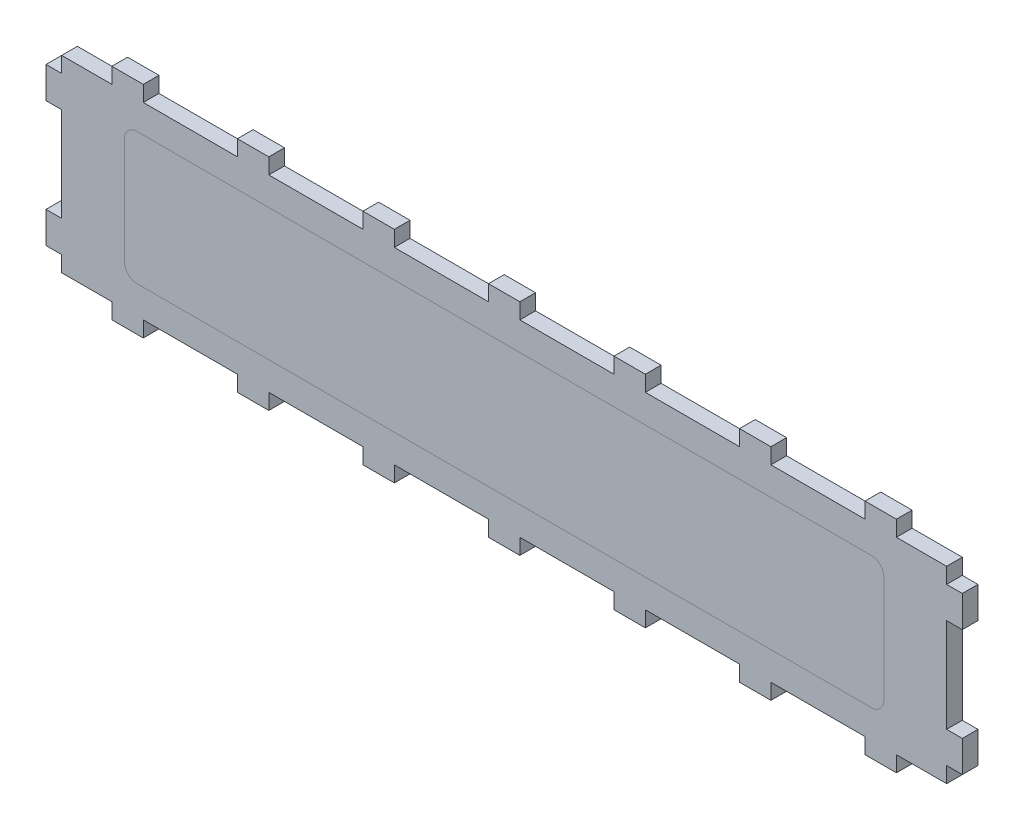
SolidWorks part; units mm, degrees
material "Maple"
ref_plane "Front" through (0, 0, 0) normal (0, 0, 1) x (1, 0, 0)
ref_plane "Top" through (0, 0, 0) normal (0, 1, 0) x (1, 0, 0)
ref_plane "Right" through (0, 0, 0) normal (1, 0, 0) x (0, 0, -1)
sketch "Sketch1" plane through (0, 0, 0) normal (0, 0, 1) x (1, 0, 0)
  line L0 (-73, 15) -> (73, 15) construction
  line L1 (-73, -17.5) -> (73, -17.5) construction
  line L2 (-73, -17.5) -> (-73, 17.5) construction
  line L3 (-73, 17.5) -> (73, 17.5) construction
  line L4 (73, -17.5) -> (73, 17.5) construction
  line L5 (-73, -17.5) -> (73, 17.5) construction
  line L6 (-73, 17.5) -> (73, -17.5) construction
  line L7 (70.5, 17.5) -> (70.5, -17.5) construction
  line L8 (-12.0378, 0) -> (10.199, 0) construction
  line L9 (0, 8.2237) -> (0, -7.5658) construction
  line L10 (-70.5, 17.5) -> (-70.5, -17.5) construction
  line L11 (-73, -15) -> (73, -15) construction
  line L12 (-70.5, -12.5) -> (-70.5, -15)
  line L13 (-70.5, -12.5) -> (-73, -12.5)
  line L14 (-73, -12.5) -> (-73, -7.5)
  line L15 (-73, -7.5) -> (-70.5, -7.5)
  line L16 (-70.5, -7.5) -> (-70.5, 7.5)
  line L17 (-70.5, -15) -> (-62.5, -15)
  line L18 (-62.5, -15) -> (-62.5, -17.5)
  line L19 (-62.5, -17.5) -> (-57.5, -17.5)
  line L20 (-57.5, -17.5) -> (-57.5, -15)
  line L21 (-57.5, -15) -> (-42.5, -15)
  line L22 (-70.5, 12.5) -> (-73, 12.5)
  line L23 (-73, 7.5) -> (-70.5, 7.5)
  line L24 (-73, 12.5) -> (-73, 7.5)
  line L25 (-70.5, 15) -> (-70.5, 12.5)
  line L26 (-42.5, -15) -> (-42.5, -17.5)
  line L27 (-42.5, -17.5) -> (-37.5, -17.5)
  line L28 (-37.5, -17.5) -> (-37.5, -15)
  line L29 (-37.5, -15) -> (-22.5, -15)
  line L30 (-22.5, -15) -> (-22.5, -17.5)
  line L31 (-22.5, -17.5) -> (-17.5, -17.5)
  line L32 (-17.5, -17.5) -> (-17.5, -15)
  line L33 (-17.5, -15) -> (-2.5, -15)
  line L34 (-2.5, -15) -> (-2.5, -17.5)
  line L35 (-2.5, -17.5) -> (2.5, -17.5)
  line L36 (2.5, -17.5) -> (2.5, -15)
  line L37 (17.5, -15) -> (2.5, -15)
  line L38 (17.5, -17.5) -> (17.5, -15)
  line L39 (22.5, -17.5) -> (17.5, -17.5)
  line L40 (22.5, -15) -> (22.5, -17.5)
  line L41 (37.5, -15) -> (22.5, -15)
  line L42 (37.5, -17.5) -> (37.5, -15)
  line L43 (42.5, -17.5) -> (37.5, -17.5)
  line L44 (42.5, -15) -> (42.5, -17.5)
  line L45 (57.5, -15) -> (42.5, -15)
  line L46 (57.5, -17.5) -> (57.5, -15)
  line L47 (62.5, -17.5) -> (57.5, -17.5)
  line L48 (62.5, -15) -> (62.5, -17.5)
  line L49 (70.5, -15) -> (62.5, -15)
  line L50 (62.5, 15) -> (62.5, 17.5)
  line L51 (70.5, -12.5) -> (73, -12.5)
  line L52 (73, -12.5) -> (73, -7.5)
  line L53 (73, -7.5) -> (70.5, -7.5)
  line L54 (70.5, -7.5) -> (70.5, 7.5)
  line L55 (73, 7.5) -> (70.5, 7.5)
  line L56 (73, 12.5) -> (73, 7.5)
  line L57 (70.5, 12.5) -> (73, 12.5)
  line L58 (70.5, 15) -> (70.5, 12.5)
  line L59 (62.5, 17.5) -> (57.5, 17.5)
  line L60 (57.5, 17.5) -> (57.5, 15)
  line L61 (57.5, 15) -> (42.5, 15)
  line L62 (42.5, 15) -> (42.5, 17.5)
  line L63 (42.5, 17.5) -> (37.5, 17.5)
  line L64 (37.5, 17.5) -> (37.5, 15)
  line L65 (37.5, 15) -> (22.5, 15)
  line L66 (22.5, 15) -> (22.5, 17.5)
  line L67 (22.5, 17.5) -> (17.5, 17.5)
  line L68 (17.5, 17.5) -> (17.5, 15)
  line L69 (17.5, 15) -> (2.5, 15)
  line L70 (2.5, 17.5) -> (2.5, 15)
  line L71 (-2.5, 17.5) -> (2.5, 17.5)
  line L72 (-2.5, 15) -> (-2.5, 17.5)
  line L73 (-17.5, 15) -> (-2.5, 15)
  line L74 (-17.5, 17.5) -> (-17.5, 15)
  line L75 (-22.5, 17.5) -> (-17.5, 17.5)
  line L76 (-22.5, 15) -> (-22.5, 17.5)
  line L77 (-37.5, 15) -> (-22.5, 15)
  line L78 (-37.5, 17.5) -> (-37.5, 15)
  line L79 (-42.5, 17.5) -> (-37.5, 17.5)
  line L80 (-42.5, 15) -> (-42.5, 17.5)
  line L81 (-57.5, 15) -> (-42.5, 15)
  line L82 (-57.5, 17.5) -> (-57.5, 15)
  line L83 (-62.5, 17.5) -> (-57.5, 17.5)
  line L84 (-62.5, 15) -> (-62.5, 17.5)
  line L85 (-70.5, 15) -> (-62.5, 15)
  line L86 (70.5, 15) -> (62.5, 15)
  line L87 (70.5, -15) -> (70.5, -12.5)
  line L89 (-58.5, -10.5) -> (58.5, -10.5)
  line L90 (-60.5, -8.5) -> (-60.5, 8.5)
  line L91 (-58.5, 10.5) -> (58.5, 10.5)
  line L92 (60.5, -8.5) -> (60.5, 8.5)
  line L93 (-60.5, -10.5) -> (60.5, 10.5) construction
  line L94 (-60.5, 10.5) -> (60.5, -10.5) construction
  arc A0 (58.5, 10.5) -> (60.5, 8.5) centre (58.5, 8.5) cw
  arc A1 (58.5, -10.5) -> (60.5, -8.5) centre (58.5, -8.5) ccw
  arc A2 (-58.5, -10.5) -> (-60.5, -8.5) centre (-58.5, -8.5) cw
  arc A3 (-60.5, 8.5) -> (-58.5, 10.5) centre (-58.5, 8.5) cw
  point P0 (0, 0)
  point P32 (-70.5, 0)
  point P47 (0, -17.5)
  point P101 (0, 0)
  dimension "D10" = 2
  dimension "D1" = 5
  dimension "D2" = 15
  dimension "D3" = 8
  dimension "D4" = 35
  dimension "D5" = 146
  dimension "D6" = 2.5
  dimension "D7" = 4.5
  dimension "D9" = 10
  dimension "D8" = 3
extrude "Boss-Extrude1" add sketch "Sketch1" along normal blind 2.5 contours L49 L87 L51 L52 L53 L54 L55 L56 L57 L58 L86 L50 L59 L60 L61 L62 L63 L64 L65 L66 L67 L68 L69 L70 L71 L72 L73 L74 L75 L76 L77 L78 L79 L80 L81 L82 L83 L84 L85 L25 L22 L24 L23 L16 L15 L14 L13 L12 L17 L18 L19 region at (-71.75, -10.9986, 0)
extrude "Boss-Extrude2" add sketch "Sketch1<3>" along normal blind 2.5 separate body contours A3 L90 A2 L89 A1 L92 A0 L91 region at (0, 0, 0)
sketch "Sketch1<3>" plane through (0, 0, 0) normal (0, 0, 1) x (1, 0, 0) same geometry as "Sketch1"
